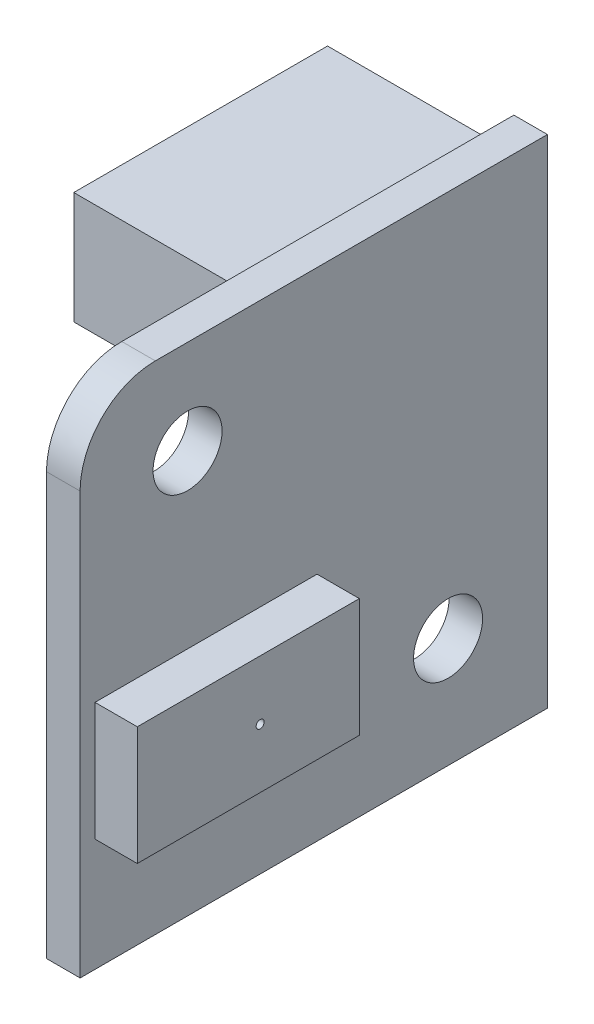
SolidWorks part; units mm, degrees
material "6061-T6 (SS)"
ref_plane "Front Plane" through (0, 0, 0) normal (0, 0, 1) x (1, 0, 0)
ref_plane "Top Plane" through (0, 0, 0) normal (0, 1, 0) x (1, 0, 0)
ref_plane "Right Plane" through (0, 0, 0) normal (1, 0, 0) x (0, 0, -1)
sketch "Sketch3" plane through (0, 0, 0) normal (1, 0, 0) x (0, 0, -1)
  line L0 (-0.56, 0) -> (0, 0) construction
  line L1 (3.66, 3.8999) -> (-4.78, -3.8999) construction
  line B0 (15.4583, -8.137) -> (-6.5127, -8.137)
  line B1 (4.6299, -2.85) -> (4.6299, 2.8499)
  line B2 (0.4199, 1.8242) -> (6.8313, 1.8242)
  line B3 (3.6433, 1.3012) -> (5.5502, 1.3012)
  line B4 (-6.5127, -8.0099) -> (-6.5127, 11.802)
  line B5 (-5.8777, -4.4539) -> (-5.8777, 8.627)
  line B6 (-5.3698, 8.627) -> (-5.3698, 13.707)
  spline B7 degree 3 poles (-2.9567, 15.358) (-4.9205, 15.358) (-6.5127, 13.7658) (-6.5127, 11.802) knots 0 0 0 0 1 1 1 1
  line B8 (-5.4886, -0.6679) -> (-5.4886, 6.468)
  spline B9 degree 3 poles (7.7113, -2.9299) (7.7113, -4.6833) (9.1329, -6.1049) (10.8863, -6.1049) knots 0 0 0 0 1 1 1 1
  spline B10 degree 3 poles (10.8863, -6.1049) (12.6397, -6.1049) (14.0613, -4.6833) (14.0613, -2.9299) knots 0 0 0 0 1 1 1 1
  line B11 (15.0773, 7.8651) -> (15.0773, -7.3749)
  line B12 (15.5852, 15.358) -> (15.5852, -8.137)
  line B13 (15.5852, 15.358) -> (-2.8298, 15.358)
  spline B14 degree 3 poles (0.8533, 10.913) (0.8533, 9.6506) (-0.1703, 8.627) (-1.4327, 8.627) knots 0 0 0 0 1 1 1 1
  line B15 (-0.7977, 10.532) -> (-0.9248, 10.6591)
  spline B16 degree 3 poles (-1.4327, 12.545) (-0.5315, 12.545) (0.1993, 11.8143) (0.1993, 10.913) knots 0 0 0 0 1 1 1 1
  spline B17 degree 3 poles (9.2544, -2.9299) (9.2544, -2.0287) (9.985, -1.298) (10.8863, -1.298) knots 0 0 0 0 1 1 1 1
  spline B18 degree 3 poles (12.5183, -2.9299) (12.5183, -3.8312) (11.7875, -4.5619) (10.8863, -4.5619) knots 0 0 0 0 1 1 1 1
  spline B19 degree 3 poles (10.8863, -4.5619) (9.985, -4.5619) (9.2544, -3.8312) (9.2544, -2.9299) knots 0 0 0 0 1 1 1 1
  line B20 (11.5213, -3.3109) -> (11.3944, -3.1839)
  spline B21 degree 3 poles (13.1723, -2.9299) (13.1723, -4.1923) (12.1487, -5.2159) (10.8863, -5.2159) knots 0 0 0 0 1 1 1 1
  line B22 (6.3885, -0.06) -> (6.3885, 6.468)
  line B23 (1.7202, 2.6499) -> (1.7202, 3.8999)
  line B24 (1.0702, 2.6499) -> (1.0702, 3.8999)
  line B25 (-5.1156, 7.2301) -> (0.9802, 7.2301)
  line B26 (3.1542, 5.5722) -> (4.7754, 5.5722)
  line B27 (-2.2029, 3.6479) -> (10.4733, 3.6479)
  line B28 (-0.2299, 2.6499) -> (-0.2299, 3.8999)
  line B29 (-1.4707, 3.8999) -> (-1.4707, 5.2062)
  line B30 (-2.2029, 1.7182) -> (-2.2029, 3.6479)
  line B31 (-1.53, 2.6499) -> (-1.53, 3.8999)
  spline B32 degree 3 poles (-1.4327, 8.627) (-2.6951, 8.627) (-3.7187, 9.6506) (-3.7187, 10.913) knots 0 0 0 0 1 1 1 1
  line B33 (2.2194, 7.7489) -> (14.7273, 7.7489)
  line B34 (5.5502, -3.8128) -> (5.5502, 1.3012)
  spline B35 degree 3 poles (13.2153, 9.594) (13.2153, 10.0126) (13.5547, 10.3522) (13.9733, 10.3522) knots 0 0 0 0 1 1 1 1
  spline B36 degree 3 poles (13.0824, 11.2941) (13.0824, 10.9577) (12.8097, 10.6849) (12.4734, 10.6849) knots 0 0 0 0 1 1 1 1
  line B37 (12.4102, 7.8651) -> (12.4102, 11.2311)
  spline B38 degree 3 poles (13.9733, 8.8359) (13.5547, 8.8359) (13.2153, 9.1753) (13.2153, 9.594) knots 0 0 0 0 1 1 1 1
  spline B39 degree 3 poles (11.8643, 11.2941) (11.8643, 11.6304) (12.137, 11.9032) (12.4734, 11.9032) knots 0 0 0 0 1 1 1 1
  line B40 (11.6737, 10.0241) -> (11.0387, 11.0401)
  line B41 (6.4413, 7.992) -> (6.4413, 11.2621)
  line B42 (0.9802, 7.992) -> (6.4413, 7.992)
  line B43 (-5.4886, 6.468) -> (6.3885, 6.468)
  line B44 (3.8992, 1.3012) -> (3.8992, 4.4121)
  line B45 (1.0702, -0.06) -> (6.3885, -0.06)
  line B46 (1.5881, -2.698) -> (3.5353, -2.698)
  line B47 (2.3701, -3.8999) -> (2.3701, -2.6501)
  line B48 (6.8313, 1.8242) -> (6.8313, 10.3039)
  line B49 (3.0202, -0.8981) -> (7.4573, -0.8981)
  line B50 (7.4573, -0.8981) -> (7.4573, 1.3162)
  line B51 (-3.6679, -6.9432) -> (-3.6679, 0.6322)
  line B52 (-0.5559, 1.1361) -> (1.5881, 1.1361)
  spline B53 degree 3 poles (4.7374, 2.9164) (4.8776, 2.9164) (4.9914, 2.8026) (4.9914, 2.6624) knots 0 0 0 0 1 1 1 1
  line B54 (3.0202, 4.4909) -> (4.9854, 4.4909)
  line B55 (11.6737, 10.0241) -> (11.6737, 11.0401)
  line B56 (2.2194, 13.7268) -> (12.9493, 13.7268)
  spline B57 degree 3 poles (9.0824, 11.2941) (9.0824, 10.9577) (8.8097, 10.6849) (8.4733, 10.6849) knots 0 0 0 0 1 1 1 1
  line B58 (10.4733, 3.6479) -> (10.4733, 11.2941)
  spline B59 degree 3 poles (6.4732, 11.6489) (6.6692, 11.6489) (6.8281, 11.49) (6.8281, 11.2941) knots 0 0 0 0 1 1 1 1
  line B60 (3.4832, 12.2842) -> (7.4634, 12.2842)
  line B61 (4.4733, 10.3039) -> (6.8313, 10.3039)
  spline B62 degree 3 poles (1.7423, 10.913) (1.7423, 12.6664) (0.3207, 14.088) (-1.4327, 14.088) knots 0 0 0 0 1 1 1 1
  line B63 (8.4733, 14.5961) -> (8.4733, 11.2941)
  spline B64 degree 3 poles (8.4733, 10.6849) (8.1369, 10.6849) (7.8642, 10.9577) (7.8642, 11.2941) knots 0 0 0 0 1 1 1 1
  line B65 (8.6511, 10.0241) -> (8.4733, 10.2018)
  spline B66 degree 3 poles (6.4732, 11.9032) (6.8096, 11.9032) (7.0823, 11.6304) (7.0823, 11.2941) knots 0 0 0 0 1 1 1 1
  line B67 (2.2194, 7.7489) -> (2.2194, 13.7268)
  line B68 (-4.3537, 14.5961) -> (8.4733, 14.5961)
  spline B69 degree 3 poles (8.6002, -2.9299) (8.6002, -1.6675) (9.6238, -0.6439) (10.8863, -0.6439) knots 0 0 0 0 1 1 1 1
  line B70 (15.0773, -7.3749) -> (3.5202, -7.3749)
  spline B71 degree 3 poles (10.8863, -5.2159) (9.6238, -5.2159) (8.6002, -4.1923) (8.6002, -2.9299) knots 0 0 0 0 1 1 1 1
  line B72 (7.4634, 1.3162) -> (7.4634, 12.2842)
  spline B73 degree 3 poles (-1.4327, 7.738) (0.3207, 7.738) (1.7423, 9.1596) (1.7423, 10.913) knots 0 0 0 0 1 1 1 1
  spline B74 degree 3 poles (-4.6077, 10.913) (-4.6077, 9.1596) (-3.1861, 7.738) (-1.4327, 7.738) knots 0 0 0 0 1 1 1 1
  spline B75 degree 3 poles (-1.4327, 9.2811) (-2.3339, 9.2811) (-3.0647, 10.0118) (-3.0647, 10.913) knots 0 0 0 0 1 1 1 1
  spline B76 degree 3 poles (9.8642, 11.2941) (9.8642, 11.6304) (10.1369, 11.9032) (10.4733, 11.9032) knots 0 0 0 0 1 1 1 1
  spline B77 degree 3 poles (10.8863, 0.2451) (9.1329, 0.2451) (7.7113, -1.1765) (7.7113, -2.9299) knots 0 0 0 0 1 1 1 1
  line B78 (2.2194, 14.8392) -> (14.7273, 14.8392)
  line B79 (9.2861, 10.1511) -> (9.2861, 10.913)
  spline B80 degree 3 poles (4.4733, 10.6849) (4.1369, 10.6849) (3.8642, 10.9577) (3.8642, 11.2941) knots 0 0 0 0 1 1 1 1
  line B81 (3.4832, 6.578) -> (3.4832, 12.2842)
  spline B82 degree 3 poles (5.4426, 4.4861) (5.4426, 4.2337) (5.2378, 4.0289) (4.9854, 4.0289) knots 0 0 0 0 1 1 1 1
  spline B83 degree 3 poles (10.8863, -0.6439) (12.1487, -0.6439) (13.1723, -1.6675) (13.1723, -2.9299) knots 0 0 0 0 1 1 1 1
  line B84 (-2.2029, 1.1742) -> (-0.5559, 1.1742)
  line B85 (12.4734, 2.9101) -> (12.4734, 11.2941)
  line B86 (-0.5559, -1.0427) -> (0.094, -1.0427)
  spline B87 degree 3 poles (14.7315, 12.9941) (14.7315, 12.5755) (14.392, 12.2359) (13.9733, 12.2359) knots 0 0 0 0 1 1 1 1
  spline B88 degree 3 poles (13.9733, 12.2359) (13.5547, 12.2359) (13.2153, 12.5755) (13.2153, 12.9941) knots 0 0 0 0 1 1 1 1
  spline B89 degree 3 poles (13.9733, 13.5491) (14.2798, 13.5491) (14.5284, 13.3006) (14.5284, 12.9941) knots 0 0 0 0 1 1 1 1
  spline B90 degree 3 poles (13.9733, 13.7522) (14.392, 13.7522) (14.7315, 13.4128) (14.7315, 12.9941) knots 0 0 0 0 1 1 1 1
  line B91 (3.8992, 5.7122) -> (4.9854, 5.7122)
  dimension "D1" = 0.56
sketch_block_instance "board7-1"
sketch_block "Block1"
sketch "Sketch4" plane through (0, 0, 0) normal (1, 0, 0) x (0, 0, -1)
  line L0 (15.5852, 15.358) -> (-2.8298, 15.358) construction
  line L1 (15.5852, 15.358) -> (15.5852, -8.137) construction
  line L2 (15.4583, -8.137) -> (-6.5127, -8.137) construction
  line L3 (-6.5127, -8.0099) -> (-6.5127, 11.802) construction
  line L4 (15.5852, 15.358) -> (-2.9567, 15.358)
  line L5 (15.5852, 15.358) -> (15.5852, -8.137)
  line L6 (15.5852, -8.137) -> (-6.5127, -8.137)
  line L7 (-6.5127, -8.137) -> (-6.5127, 11.802)
  line L8 (-1.4327, 12.545) -> (-1.4327, 9.2811) construction
  line L9 (10.8863, -1.298) -> (10.8863, -4.5619) construction
  circle A0 centre (-1.4327, 10.9131) radius 1.6319
  circle A1 centre (10.8863, -2.93) radius 1.632
  circle A2 centre (0, 0) radius 0.1905
  spline S0 degree 3 poles (-1052.8264, -1682.4396) (1312.4187, 1548.6565) (-1539.8468, -1303.5531) (1691.3406, 1061.6601) knots -9.999116 -9.999116 -9.999116 -9.999116 10.999181 10.999181 10.999181 10.999181 only from (-2.9567, 15.358) to (-6.5127, 11.802) construction
  spline S1 degree 3 poles (-2.9567, 15.358) (-4.9205, 15.358) (-6.5127, 13.7658) (-6.5127, 11.802) knots 0 0 0 0 1 1 1 1
  dimension "D1" = 0.381
extrude "Boss-Extrude1" add sketch "Sketch4" along normal blind 1.5875
sketch "Sketch5" plane through (1.5875, 0, 0) normal (1, 0, 0) x (0, 0, -1)
  line L1 (-5.81, -2.8) -> (4.69, -2.8)
  line L2 (-5.81, -2.8) -> (-5.81, 2.8)
  line L3 (-5.81, 2.8) -> (4.69, 2.8)
  line L4 (4.69, -2.8) -> (4.69, 2.8)
  line L5 (-5.81, -2.8) -> (4.69, 2.8) construction
  line L6 (-5.81, 2.8) -> (4.69, -2.8) construction
  circle A0 centre (0, 0) radius 0.1905 construction
  circle A1 centre (0, 0) radius 0.1905
  point P4 (-0.56, 0)
  dimension "D1" = 10.5
  dimension "D2" = 5.6
extrude "Boss-Extrude2" add sketch "Sketch5" along normal blind 2
sketch "Sketch6" plane through (1.5875, 0, 0) normal (1, 0, 0) x (0, 0, -1)
  line L0 (8.4733, 14.5961) -> (8.4733, 11.2941) construction
  line L1 (2.4733, 14.8941) -> (14.4733, 14.8941)
  line L2 (2.4733, 14.8941) -> (2.4733, 9.5941)
  line L3 (2.4733, 9.5941) -> (14.4733, 9.5941)
  line L4 (14.4733, 14.8941) -> (14.4733, 9.5941)
  line L5 (2.4733, 14.8941) -> (14.4733, 9.5941) construction
  line L6 (2.4733, 9.5941) -> (14.4733, 14.8941) construction
  point P4 (8.4733, 12.2441)
  dimension "D1" = 5.3
  dimension "D2" = 12
  dimension "D3" = 1.7
extrude "Boss-Extrude3" [suppressed] add sketch "Sketch6" along normal blind 7.7
extrude "Boss-Extrude4" add sketch "Sketch6<2>" against normal blind 7.7 from vertex starting at point (0, 15.358, -15.5852)
sketch "Sketch6<2>" plane through (1.5875, 0, 0) normal (1, 0, 0) x (0, 0, -1) same geometry as "Sketch6"
